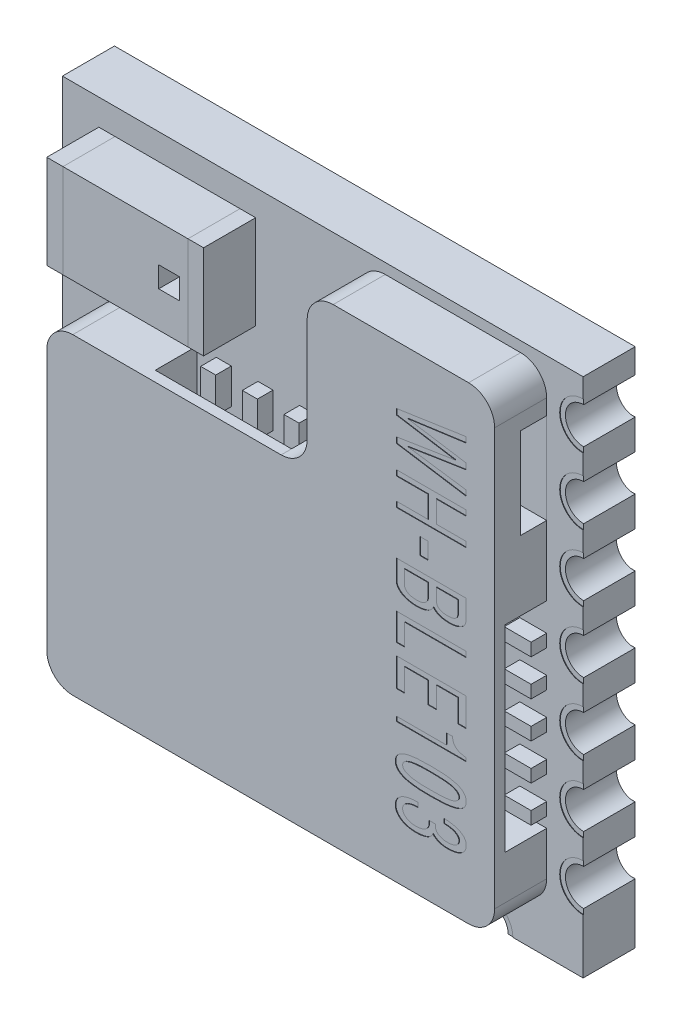
SolidWorks part; units mm, degrees
ref_plane "前视基准面" through (0, 0, 0) normal (0, 0, 1) x (1, 0, 0)
ref_plane "上视基准面" through (0, 0, 0) normal (0, 1, 0) x (1, 0, 0)
ref_plane "右视基准面" through (0, 0, 0) normal (1, 0, 0) x (0, 0, -1)
sketch "草图1" plane through (0, 0, 0) normal (0, 0, 1) x (1, 0, 0)
  line L1 (-5, 5) -> (5, 5)
  line L2 (-5, 5) -> (-5, -5)
  line L3 (-5, -5) -> (5, -5)
  line L4 (5, 5) -> (5, -5)
  line L5 (-5, 5) -> (5, -5) construction
  line L6 (-5, -5) -> (5, 5) construction
  point P0 (0, 0)
extrude "凸台-拉伸1" add sketch "草图1" along normal blind 1
sketch "草图2" plane through (0, 0, 1) normal (0, 0, 1) x (1, 0, 0)
  line L0 (5, -5) -> (5, 5) construction
  line L1 (-5, -5) -> (5, -5) construction
  line L2 (-5, 5) -> (-5, -5) construction
  line L3 (5, 5) -> (-5, 5) construction
  circle A0 centre (5, -3.5) radius 0.35
  circle A1 centre (5, -2.22) radius 0.35
  circle A2 centre (5, -0.94) radius 0.35
  circle A3 centre (5, 0.34) radius 0.35
  circle A4 centre (5, 1.62) radius 0.35
  circle A5 centre (5, 2.9) radius 0.35
  circle A6 centre (5, 4.18) radius 0.35
  circle A7 centre (-3.2, -5) radius 0.35
  circle A8 centre (-1.92, -5) radius 0.35
  circle A9 centre (-0.64, -5) radius 0.35
  circle A10 centre (0.64, -5) radius 0.35
  circle A11 centre (1.92, -5) radius 0.35
  circle A12 centre (3.2, -5) radius 0.35
  circle A13 centre (-5, 0.34) radius 0.35
  circle A14 centre (-5, -0.94) radius 0.35
  circle A15 centre (-5, -2.22) radius 0.35
  circle A16 centre (-5, -3.5) radius 0.35
  dimension "D1" = 1.5
  dimension "D3" = 1.8
  dimension "D5" = 4.66
  dimension "D2" = 7
  dimension "D4" = 6
  dimension "D6" = 4
extrude "切除-拉伸1" cut sketch "草图2" against normal blind 1
sketch "草图3" plane through (0, 0, 1) normal (0, 0, 1) x (1, 0, 0)
  line L0 (5, 4.53) -> (4.05, 4.53)
  line L1 (4.05, 4.53) -> (4.05, 3.83)
  line L2 (4.05, 3.83) -> (5, 3.83)
  line L3 (5, 4.53) -> (5, 3.83)
  line L4 (5, 2.55) -> (5, 3.25)
  line L5 (5, 3.25) -> (4.05, 3.25)
  line L6 (4.05, 3.25) -> (4.05, 2.55)
  line L7 (4.05, 2.55) -> (5, 2.55)
  line L8 (5, 1.27) -> (5, 1.97)
  line L9 (5, 1.97) -> (4.05, 1.97)
  line L10 (4.05, 1.97) -> (4.05, 1.27)
  line L11 (4.05, 1.27) -> (5, 1.27)
  line L12 (5, -0.01) -> (5, 0.69)
  line L13 (5, 0.69) -> (4.05, 0.69)
  line L14 (4.05, 0.69) -> (4.05, 0)
  line L15 (4.05, 0) -> (5, -0.01)
  line L16 (5, -0.59) -> (4.05, -0.59)
  line L17 (4.05, -0.59) -> (4.05, -1.29)
  line L18 (4.05, -1.29) -> (5, -1.29)
  line L19 (5, -1.29) -> (5, -0.59)
  line L20 (5, -2.57) -> (5, -1.87)
  line L21 (5, -1.87) -> (4.05, -1.87)
  line L22 (4.05, -1.87) -> (4.05, -2.57)
  line L23 (4.05, -2.57) -> (5, -2.57)
  line L24 (5, -3.85) -> (5, -3.15)
  line L25 (5, -3.15) -> (4.05, -3.15)
  line L26 (4.05, -3.15) -> (4.05, -3.85)
  line L27 (4.05, -3.85) -> (5, -3.85)
  line L28 (-3.55, -5) -> (-3.55, -4.05)
  line L29 (-3.55, -4.05) -> (-2.85, -4.05)
  line L30 (-2.85, -4.05) -> (-2.85, -5)
  line L31 (-2.85, -5) -> (-3.55, -5)
  line L32 (-2.27, -5) -> (-2.27, -4.05)
  line L33 (-2.27, -4.05) -> (-1.57, -4.05)
  line L34 (-1.57, -4.05) -> (-1.57, -5)
  line L35 (-1.57, -5) -> (-2.27, -5)
  line L36 (-0.99, -5) -> (-0.99, -4.05)
  line L37 (-0.99, -4.05) -> (-0.29, -4.05)
  line L38 (-0.29, -4.05) -> (-0.29, -5)
  line L39 (-0.29, -5) -> (-0.99, -5)
  line L40 (0.29, -5) -> (0.29, -4.05)
  line L41 (0.29, -4.05) -> (0.99, -4.05)
  line L42 (0.99, -4.05) -> (0.99, -5)
  line L43 (0.99, -5) -> (0.29, -5)
  line L44 (1.57, -5) -> (1.57, -4.05)
  line L45 (1.57, -4.05) -> (2.27, -4.05)
  line L46 (2.27, -4.05) -> (2.27, -5)
  line L47 (2.27, -5) -> (1.57, -5)
  line L48 (2.85, -5) -> (2.85, -4.05)
  line L49 (2.85, -4.05) -> (3.55, -4.05)
  line L50 (3.55, -4.05) -> (3.55, -5)
  line L51 (3.55, -5) -> (2.85, -5)
  line L52 (-5, 0.69) -> (-4.0499, 0.69)
  line L53 (-4.0499, 0.69) -> (-4.0499, -0.01)
  line L54 (-4.0499, -0.01) -> (-5, -0.01)
  line L55 (-5, -0.01) -> (-5, 0.69)
  line L56 (-5, -0.59) -> (-4.0499, -0.59)
  line L57 (-4.0499, -0.59) -> (-4.0499, -1.29)
  line L58 (-4.0499, -1.29) -> (-5, -1.29)
  line L59 (-5, -1.29) -> (-5, -0.59)
  line L60 (-5, -1.87) -> (-4.0499, -1.87)
  line L61 (-4.0499, -1.87) -> (-4.0499, -2.57)
  line L62 (-4.0499, -2.57) -> (-5, -2.57)
  line L63 (-5, -2.57) -> (-5, -1.87)
  line L64 (-5, -3.15) -> (-4.0499, -3.15)
  line L65 (-4.0499, -3.15) -> (-4.0499, -3.85)
  line L66 (-4.0499, -3.85) -> (-5, -3.85)
  line L67 (-5, -3.85) -> (-5, -3.15)
  arc A0 (5, -1.87) -> (5, -2.57) centre (5, -2.22) ccw construction
  arc A1 (5, -3.15) -> (5, -3.85) centre (5, -3.5) ccw construction
  dimension "D1" = 6
  dimension "D2" = 4
extrude "切除-拉伸2" [suppressed] cut sketch "草图3" against normal blind 0.01
extrude "切除-拉伸4" cut sketch "草图3<2>" along normal blind 0.01 from surface starting at face at (0.7618, -1.7311, 0)
sketch "草图3<2>" plane through (0, 0, 1) normal (0, 0, 1) x (1, 0, 0) same geometry as "草图3"
sketch "草图4" plane through (0, 0, 1) normal (0, 0, 1) x (1, 0, 0)
  line L1 (4.3, 4.8) -> (4.3, -4.2)
  line L2 (4.3, -4.2) -> (-2.8663, -4.2)
  line L7 (5, 4.53) -> (5, 5) construction
  line L8 (4.3, 4.8) -> (0.7, 4.8)
  line L9 (0.7, 4.8) -> (0.7, 1.8)
  line L10 (0.7, 1.8) -> (-4.3, 1.8)
  line L11 (-4.3, 1.8) -> (-4.3, -4.2)
  line L12 (-4.3, -4.2) -> (-2.8663, -4.2)
  line L13 (-5, 5) -> (-5, 0.69) construction
  line L14 (5, 5) -> (-5, 5) construction
  line L15 (3.55, -5) -> (5, -5) construction
  point P10 (5, 4.765)
  point P16 (4.275, -5)
  dimension "D1" = 0.7
  dimension "D2" = 0.7
  dimension "D3" = 0.2
  dimension "D4" = 0.8
extrude "凸台-拉伸2" add sketch "草图4" along normal blind 1
sketch "草图5" plane through (0, 0, 1) normal (0, 0, 1) x (1, 0, 0)
  circle A0 centre (-5, 0.34) radius 0.45
  circle A1 centre (-5, -0.94) radius 0.45
  circle A2 centre (-5, -2.22) radius 0.45
  circle A3 centre (-5, -3.5) radius 0.45
  circle A4 centre (-3.2, -5) radius 0.45
  circle A5 centre (-1.92, -5) radius 0.45
  circle A6 centre (-0.64, -5) radius 0.45
  circle A7 centre (0.64, -5) radius 0.45
  circle A8 centre (1.92, -5) radius 0.45
  circle A9 centre (3.2, -5) radius 0.45
  circle A10 centre (5, -3.5) radius 0.45
  circle A11 centre (5, -2.22) radius 0.45
  circle A12 centre (5, -0.94) radius 0.45
  circle A13 centre (5, 0.34) radius 0.45
  circle A14 centre (5, 1.62) radius 0.45
  circle A15 centre (5, 2.9) radius 0.45
  circle A16 centre (5, 4.18) radius 0.45
  dimension "D1" = 4
  dimension "D2" = 6
  dimension "D3" = 7
extrude "切除-拉伸5" cut sketch "草图5" against normal blind 0.01
sketch "草图6" plane through (0, 0, 1) normal (0, 0, 1) x (1, 0, 0)
  line L0 (-4.3, 4.5) -> (-4.3, 2.7)
  line L1 (-4.3, 4.5) -> (-3.9889, 4.5)
  line L2 (-3.9889, 4.5) -> (-3.9889, 2.7)
  line L3 (-3.9889, 2.7) -> (-4.3, 2.7)
  line L4 (-4.3, 1.8) -> (-4.3, -4.2) construction
  line L5 (5, 5) -> (-5, 5) construction
  line L6 (-3.9889, 4.5) -> (-1.5889, 4.5)
  line L7 (-1.5889, 4.5) -> (-1.5889, 2.7)
  line L8 (-1.5889, 2.7) -> (-3.9889, 2.7)
  line L9 (-1.5889, 4.5) -> (-1.2889, 4.5)
  line L10 (-1.2889, 4.5) -> (-1.2889, 2.7)
  line L11 (-1.2889, 2.7) -> (-1.5889, 2.7)
  dimension "D1" = 0.5
  dimension "D2" = 1.8
extrude "凸台-拉伸3" add sketch "草图6" along normal blind 1 separate body contours L3 L2 L1 L0 region at (-4.1444, 3.6, 1)
extrude "凸台-拉伸4" add sketch "草图6<3>" along normal blind 1 separate body contours L8 L7 L6 L2 region at (-2.7889, 3.6, 1)
sketch "草图6<3>" plane through (0, 0, 1) normal (0, 0, 1) x (1, 0, 0) same geometry as "草图6"
extrude "凸台-拉伸6" add sketch "草图6<4>" along normal blind 1 separate body contours L11 L10 L9 L7 region at (-1.4389, 3.6, 1)
sketch "草图6<4>" plane through (0, 0, 1) normal (0, 0, 1) x (1, 0, 0) same geometry as "草图6"
sketch "草图7" plane through (0, 0, 2) normal (0, 0, 1) x (1, 0, 0)
  line L1 (-2.1511, 3.7863) -> (-1.7511, 3.7863)
  line L2 (-2.1511, 3.7863) -> (-2.1511, 3.3863)
  line L3 (-2.1511, 3.3863) -> (-1.7511, 3.3863)
  line L4 (-1.7511, 3.7863) -> (-1.7511, 3.3863)
  line L5 (-2.1511, 3.7863) -> (-1.7511, 3.3863) construction
  line L6 (-2.1511, 3.3863) -> (-1.7511, 3.7863) construction
  point P0 (-1.9511, 3.5863)
extrude "切除-拉伸6" cut sketch "草图7" against normal blind 0.5
sketch "草图9" plane through (0, 0, 2) normal (0, 0, 1) x (1, 0, 0)
  line L0 (2.4117, 4.2468) -> (2.4117, -3.5926) construction
  text T0 "WH-BLE103" font "Helvetica Neue" height in points 4
extrude "切除-拉伸7" cut sketch "草图9" against normal blind 0.01
fillet "圆角1" radius 0.5 6 edges at (4.3, -4.2, 1.5) (0.7, 4.8, 1.5) (0.7, 1.8, 1.5) (-4.3, 1.8, 1.5) (-4.3, -4.2, 1.5) (4.3, 4.8, 1.5)
sketch "草图10" plane through (0, -4.2, 0) normal (0, -1, 0) x (1, 0, 0)
  line L0 (-2.8553, 1) -> (-2.8553, 1.8)
  line L1 (-3.8, 1) -> (3.8, 1) construction
  line L2 (-2.8553, 1.8) -> (3.3197, 1.8)
  line L3 (3.3197, 1.8) -> (3.3197, 1)
  line L4 (3.3197, 1) -> (-2.8553, 1)
extrude "切除-拉伸8" cut sketch "草图10" against normal blind 1
sketch "草图11" plane through (0.7, 0, 0) normal (-1, 0, 0) x (0, 0, 1)
  line L0 (1, 2.7) -> (1.8, 2.7)
  line L2 (1.8, 2.7) -> (1.8, 3.9999)
  line L3 (1.8, 3.9999) -> (1, 3.9999)
  line L4 (1, 4.5) -> (1, 2.7) construction
  line L5 (1, 3.9999) -> (1, 2.7)
extrude "切除-拉伸9" cut sketch "草图11" against normal blind 1
sketch "草图12" plane through (0, 1.8, 0) normal (0, 1, 0) x (1, 0, 0)
  line L0 (0.2, -1) -> (0.2, -1.8)
  line L1 (0.2, -2) -> (0.2, -1) construction
  line L2 (0.2, -1.8) -> (-2.4166, -1.8)
  line L3 (-2.4166, -1.8) -> (-2.4166, -1)
  line L4 (-3.9889, -1) -> (-1.5889, -1) construction
  line L5 (-2.4166, -1) -> (0.2, -1)
extrude "切除-拉伸10" cut sketch "草图12" against normal blind 1
sketch "草图13" plane through (-4.3, 0, 0) normal (-1, 0, 0) x (0, 0, 1)
  line L0 (1, 0.946) -> (1.8, 0.946)
  line L1 (1, 1.3) -> (1, -3.7) construction
  line L2 (1.8, 0.946) -> (1.8, -3.2387)
  line L3 (1.8, -3.2387) -> (1, -3.2387)
  line L4 (1, -3.2387) -> (1, 0.946)
extrude "切除-拉伸11" cut sketch "草图13" against normal blind 1
sketch "草图14" plane through (4.3, 0, 0) normal (1, 0, 0) x (0, 0, -1)
  line L0 (-1, -2.86) -> (-1.8, -2.86)
  line L1 (-1, -3.05) -> (-1, -2.67) construction
  line L2 (-1.8, -2.86) -> (-1.8, 0.9238)
  line L3 (-1.8, 0.9238) -> (-1, 0.9238)
  line L4 (-1, 0.79) -> (-1, 1.17) construction
  line L5 (-1, 0.9238) -> (-1, -2.86)
  line L6 (-1, 2.26) -> (-1.5, 2.26)
  line L7 (-1, 2.07) -> (-1, 2.45) construction
  line L8 (-1.5, 2.26) -> (-1.5, 4.0016)
  line L9 (-1.5, 4.0016) -> (-0.99, 4.0016)
  line L10 (-0.99, 4.53) -> (-0.99, 3.83) construction
  line L11 (-0.99, 4.0016) -> (-1, 2.26)
extrude "切除-拉伸12" cut sketch "草图14" against normal blind 1
sketch "草图15" plane through (0, 0, 1) normal (0, 0, 1) x (1, 0, 0)
  line L0 (4.3, -2.66) -> (3.7841, -2.66)
  line L1 (4.3, -3.7) -> (4.3, 4.3) construction
  line L2 (3.7841, -2.66) -> (3.7841, -2.4151)
  line L3 (3.7841, -2.4151) -> (4.3, -2.4151)
  line L4 (4.3, -2.4151) -> (4.3, -2.66)
  line L5 (4.3, -1.96) -> (3.7841, -1.96)
  line L6 (3.7841, -1.96) -> (3.7841, -1.7151)
  line L7 (3.7841, -1.7151) -> (4.3, -1.7151)
  line L8 (4.3, -1.7151) -> (4.3, -1.96)
  line L9 (4.3, -1.26) -> (3.7841, -1.26)
  line L10 (3.7841, -1.26) -> (3.7841, -1.0151)
  line L11 (3.7841, -1.0151) -> (4.3, -1.0151)
  line L12 (4.3, -1.0151) -> (4.3, -1.26)
  line L13 (4.3, -0.56) -> (3.7841, -0.56)
  line L14 (3.7841, -0.56) -> (3.7841, -0.3151)
  line L15 (3.7841, -0.3151) -> (4.3, -0.3151)
  line L16 (4.3, -0.3151) -> (4.3, -0.56)
  line L17 (4.3, 0.14) -> (3.7841, 0.14)
  line L18 (3.7841, 0.14) -> (3.7841, 0.3849)
  line L19 (3.7841, 0.3849) -> (4.3, 0.3849)
  line L20 (4.3, 0.3849) -> (4.3, 0.14)
  dimension "D1" = 5
extrude "凸台-拉伸7" add sketch "草图15" along normal blind 0.3
sketch "草图16" plane through (0, 0, 1) normal (0, 0, 1) x (1, 0, 0)
  line L0 (-2.5827, -3.7032) -> (-1.7814, -3.7032)
  line L1 (-1.7814, -3.7032) -> (-1.7814, -3.4138)
  line L2 (-1.7814, -3.4138) -> (-2.5827, -3.4138)
  line L3 (-2.5827, -3.4138) -> (-2.5827, -3.7032)
  line L4 (-0.6814, -3.7032) -> (-0.6814, -3.4138)
  line L5 (-0.6814, -3.4138) -> (-1.4827, -3.4138)
  line L6 (-1.4827, -3.4138) -> (-1.4827, -3.7032)
  line L7 (-1.4827, -3.7032) -> (-0.6814, -3.7032)
  line L8 (0.4186, -3.7032) -> (0.4186, -3.4138)
  line L9 (0.4186, -3.4138) -> (-0.3827, -3.4138)
  line L10 (-0.3827, -3.4138) -> (-0.3827, -3.7032)
  line L11 (-0.3827, -3.7032) -> (0.4186, -3.7032)
  line L12 (1.5186, -3.7032) -> (1.5186, -3.4138)
  line L13 (1.5186, -3.4138) -> (0.7173, -3.4138)
  line L14 (0.7173, -3.4138) -> (0.7173, -3.7032)
  line L15 (0.7173, -3.7032) -> (1.5186, -3.7032)
  line L16 (2.6186, -3.7032) -> (2.6186, -3.4138)
  line L17 (2.6186, -3.4138) -> (1.8173, -3.4138)
  line L18 (1.8173, -3.4138) -> (1.8173, -3.7032)
  line L19 (1.8173, -3.7032) -> (2.6186, -3.7032)
  dimension "D1" = 5
extrude "凸台-拉伸8" add sketch "草图16" along normal blind 0.3
sketch "草图17" plane through (0, 0, 1) normal (0, 0, 1) x (1, 0, 0)
  line L0 (-4.3, 0.6657) -> (-3.5068, 0.6657)
  line L1 (-4.3, 1.3) -> (-4.3, -3.7) construction
  line L2 (-3.5068, 0.6657) -> (-3.5068, 0.3541)
  line L3 (-3.5068, 0.3541) -> (-4.3, 0.3541)
  line L4 (-4.3, 0.3541) -> (-4.3, 0.6657)
  line L5 (-4.3, -0.1343) -> (-3.5068, -0.1343)
  line L6 (-3.5068, -0.1343) -> (-3.5068, -0.4459)
  line L7 (-4.3, -0.4459) -> (-4.3, -0.1343)
  line L8 (-3.5068, -0.4459) -> (-4.3, -0.4459)
  line L9 (-4.3, -0.9343) -> (-3.5068, -0.9343)
  line L10 (-3.5068, -0.9343) -> (-3.5068, -1.2459)
  line L11 (-4.3, -1.2459) -> (-4.3, -0.9343)
  line L12 (-3.5068, -1.2459) -> (-4.3, -1.2459)
  line L13 (-4.3, -1.7343) -> (-3.5068, -1.7343)
  line L14 (-3.5068, -1.7343) -> (-3.5068, -2.0459)
  line L15 (-4.3, -2.0459) -> (-4.3, -1.7343)
  line L16 (-3.5068, -2.0459) -> (-4.3, -2.0459)
  line L17 (-4.3, -2.5343) -> (-3.5068, -2.5343)
  line L18 (-3.5068, -2.5343) -> (-3.5068, -2.8459)
  line L19 (-4.3, -2.8459) -> (-4.3, -2.5343)
  line L20 (-3.5068, -2.8459) -> (-4.3, -2.8459)
  dimension "D1" = 5
extrude "凸台-拉伸9" add sketch "草图17" along normal blind 0.3
sketch "草图18" plane through (0, 0, 1) normal (0, 0, 1) x (1, 0, 0)
  line L0 (-0.1558, 1.8) -> (-0.1558, 1.1241)
  line L1 (0.2, 1.8) -> (-3.8, 1.8) construction
  line L2 (-0.1558, 1.1241) -> (-0.4452, 1.1241)
  line L3 (-0.4452, 1.1241) -> (-0.4452, 1.8)
  line L4 (-0.4452, 1.8) -> (-0.1558, 1.8)
  line L5 (-0.9558, 1.8) -> (-0.9558, 1.1241)
  line L6 (-0.9558, 1.1241) -> (-1.2452, 1.1241)
  line L7 (-1.2452, 1.1241) -> (-1.2452, 1.8)
  line L8 (-1.2452, 1.8) -> (-0.9558, 1.8)
  line L9 (-1.7558, 1.8) -> (-1.7558, 1.1241)
  line L10 (-1.7558, 1.1241) -> (-2.0452, 1.1241)
  line L11 (-2.0452, 1.1241) -> (-2.0452, 1.8)
  line L12 (-2.0452, 1.8) -> (-1.7558, 1.8)
  dimension "D1" = 3
extrude "凸台-拉伸10" add sketch "草图18" along normal blind 0.3
